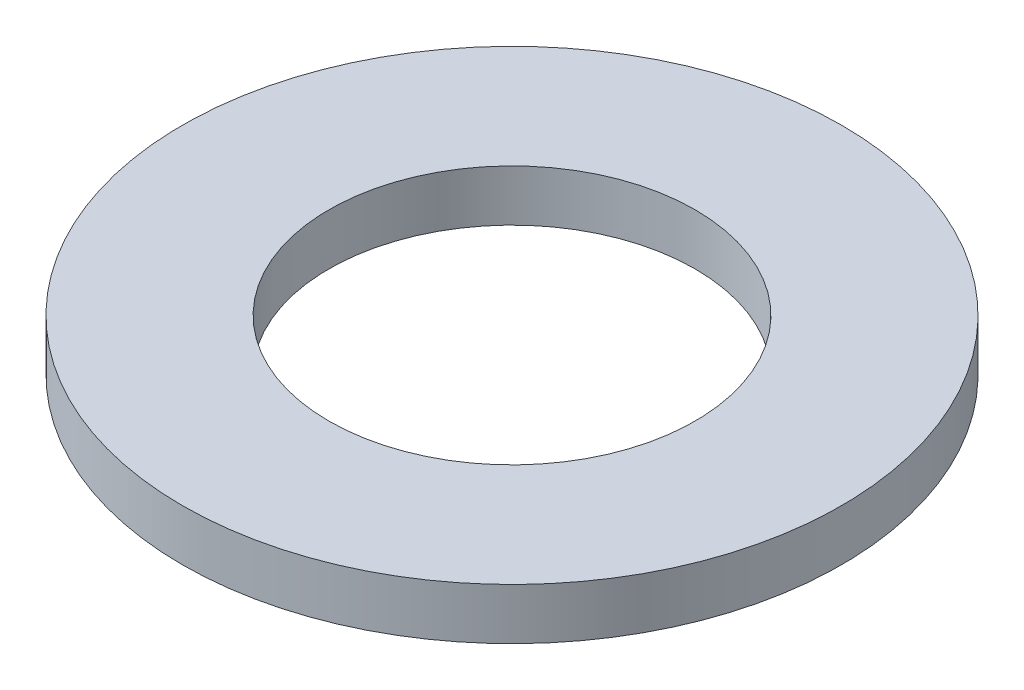
SolidWorks part; units mm, degrees
ref_plane "Front Plane" through (0, 0, 0) normal (0, 0, 1) x (1, 0, 0)
ref_plane "Top Plane" through (0, 0, 0) normal (0, 1, 0) x (1, 0, 0)
ref_plane "Right Plane" through (0, 0, 0) normal (1, 0, 0) x (0, 0, -1)
sketch "Sketch1" plane through (0, 0, 0) normal (0, 1, 0) x (1, 0, 0)
  circle A0 centre (0, 0) radius 90
  dimension "FLANGE_OD" = 180
extrude "Boss-Extrude1" add sketch "Sketch1" along normal blind 14
sketch "Sketch2" plane through (0, 0, 0) normal (0, 1, 0) x (1, 0, 0)
  circle A0 centre (0, 0) radius 50
  dimension "BORE_D" = 100
extrude "Cut-Extrude1" cut sketch "Sketch2" along normal through all
sketch "Sketch3" plane through (0, 14, 0) normal (0, 1, 0) x (1, 0, 0)
  circle A0 centre (0, 0) radius 39.7818 construction
  circle A1 centre (-39.7818, 0) radius 1.5719
  dimension "BOLT_D" = 3.1437
  dimension "BOLT_PCD" = 79.5636
extrude "Cut-Extrude2" cut sketch "Sketch3" against normal blind 11.9872 rebuild error yes
pattern_circular "CirPattern1" count 6 over 360 rebuild error yes
